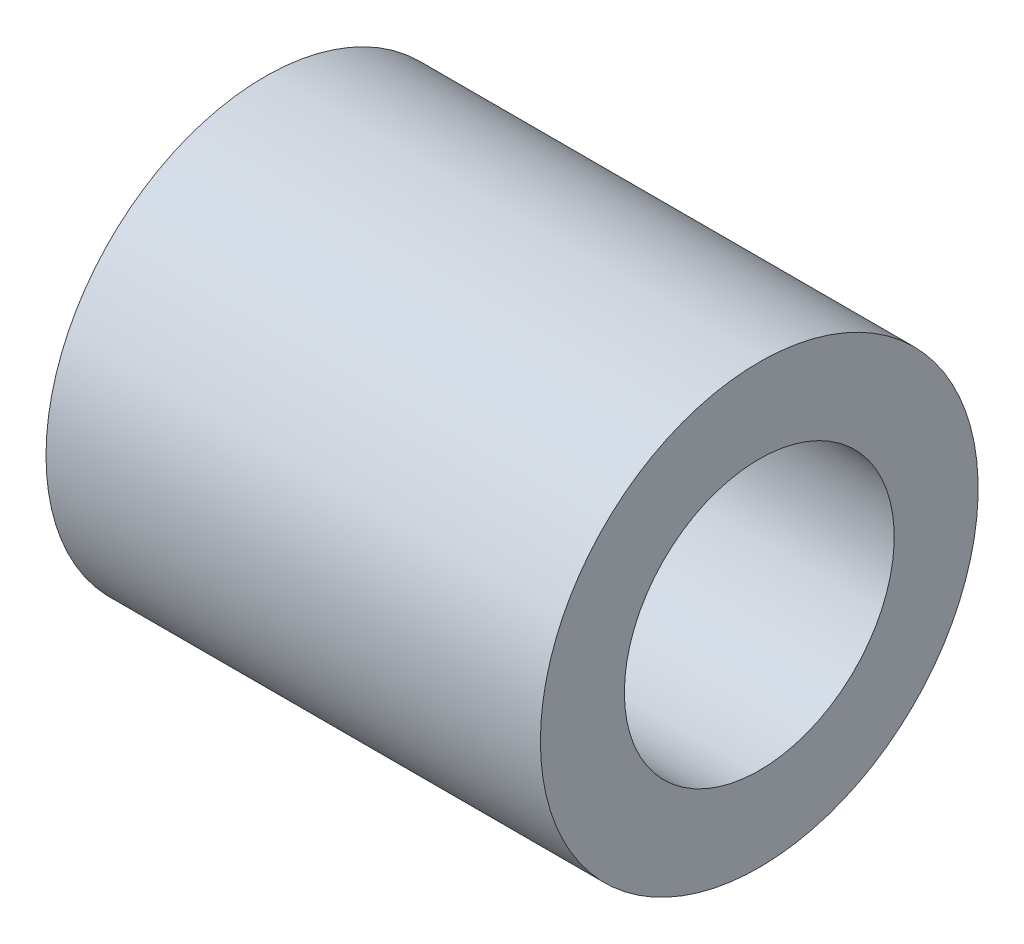
SolidWorks part; units mm, degrees
material "PLA"
ref_plane "Front Plane" through (0, 0, 0) normal (0, 0, 1) x (1, 0, 0)
ref_plane "Top Plane" through (0, 0, 0) normal (0, 1, 0) x (1, 0, 0)
ref_plane "Right Plane" through (0, 0, 0) normal (1, 0, 0) x (0, 0, -1)
sketch "Sketch1" plane through (0, 0, 0) normal (1, 0, 0) x (0, 0, -1)
  circle A0 centre (0, 0) radius 3.3274
  circle A1 centre (0, 0) radius 5.3975
  dimension "D1" = 6.6548
  dimension "D2" = 10.795
extrude "Boss-Extrude1" add sketch "Sketch1" along normal blind 12.192
